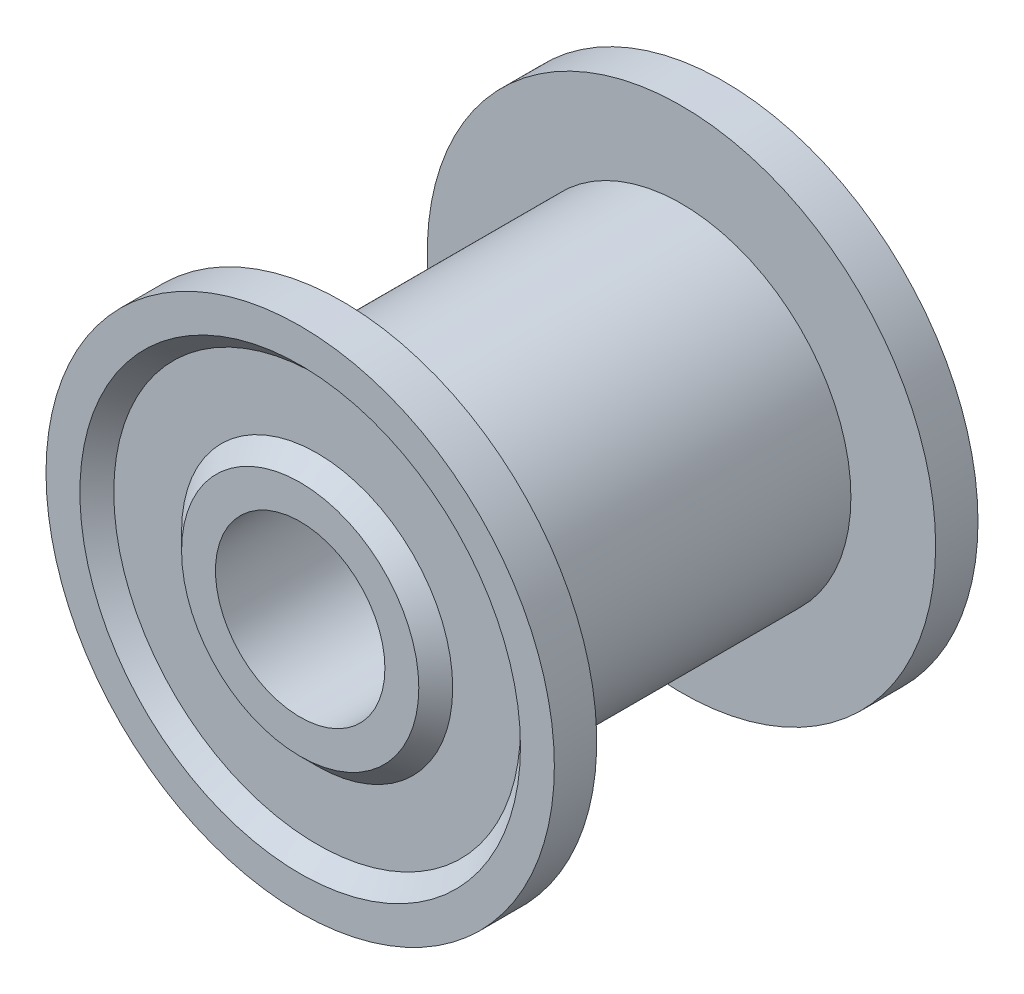
SolidWorks part; units mm, degrees
ref_plane "Alzado" through (0, 0, 0) normal (0, 0, 1) x (1, 0, 0)
ref_plane "Planta" through (0, 0, 0) normal (0, 1, 0) x (1, 0, 0)
ref_plane "Vista lateral" through (0, 0, 0) normal (1, 0, 0) x (0, 0, -1)
sketch "Croquis1" plane through (0, 0, 0) normal (0, 0, 1) x (1, 0, 0)
  circle A0 centre (0, 0) radius 5
  circle A1 centre (0, 0) radius 15
  dimension "D1" = 10
  dimension "D2" = 30
extrude "Saliente-Extruir1" add sketch "Croquis1" along normal blind 25
sketch "Croquis3" plane through (0, 0, 0) normal (1, 0, 0) x (0, 0, -1)
  line L0 (0, 15) -> (-25, 15) construction
  line L1 (-2.5, 10) -> (-22.5, 10)
  line L2 (-2.5, 10) -> (-2.5, 20)
  line L3 (-2.5, 20) -> (-22.5, 20)
  line L4 (-22.5, 10) -> (-22.5, 20)
  line L5 (-2.5, 10) -> (-22.5, 20) construction
  line L6 (-2.5, 20) -> (-22.5, 10) construction
  point P0 (-12.5, 15)
  dimension "D1" = 20
ref_axis "Eje1" through (0, 0, 25) along (0, 0, -1)
revolve "Cortar-Revolución1" cut sketch "Croquis3" angle 360 about axis through (0, 0, 25) along (0, 0, -1)
sketch "Croquis4" plane through (0, 0, 25) normal (0, 0, 1) x (1, 0, 0)
  circle A0 centre (0, 0) radius 7
  circle A1 centre (0, 0) radius 13
extrude "Cortar-Extruir1" cut sketch "Croquis4" against normal blind 1
chamfer "Chaflán1" distance 1 angle 45 2 edges at (13, 0, 24) (7, 0, 24)
ref_plane "Plano1" through (0, 0, 12.5) normal (0, 0, 1) x (1, 0, 0)
mirror "Simetría2" about plane through (0, 0, 12.5) normal (0, 0, 1) of "Chaflán1", "Cortar-Extruir1"
